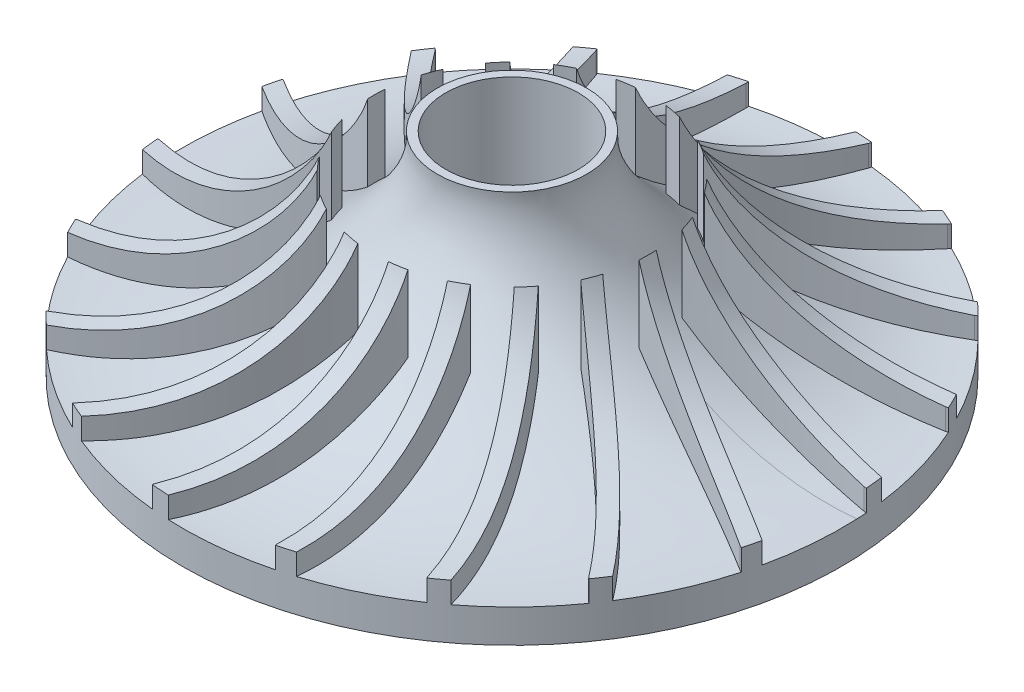
SolidWorks part; units mm, degrees
material "Aluminum Bronze"
ref_plane "Front Plane" through (0, 0, 0) normal (0, 0, 1) x (1, 0, 0)
ref_plane "Top Plane" through (0, 0, 0) normal (0, 1, 0) x (1, 0, 0)
ref_plane "Right Plane" through (0, 0, 0) normal (1, 0, 0) x (0, 0, -1)
curve "Shroud Curve"
curve "Impeller Curve"
curve "Blade Curve"
sketch "Sketch2" plane through (0, 0, 0) normal (0, 0, 1) x (1, 0, 0)
  line L0 (12.3936, 20.32) -> (31.524, 20.32)
  line L1 (31.524, 20.32) -> (31.524, 5.2084)
  spline S0 degree 3 poles (-987.5158, 25.9904) (14.3924, 25.4096) (12.3838, 22.8501) (12.394, 20.2062) (12.3983, 20.0433) (12.4153, 19.7646) (12.4464, 19.455) (12.5, 19.0868) (12.5725, 18.7015) (12.668, 18.288) (12.7893, 17.8459) (12.939, 17.3754) (13.1199, 16.8765) (13.3352, 16.3498) (13.5878, 15.7963) (13.8846, 15.2103) (14.2339, 14.5865) (14.6461, 13.9208) (15.1337, 13.2093) (15.7166, 12.4431) (16.4608, 11.5686) (17.3717, 10.6312) (18.3895, 9.7284) (19.3933, 8.9559) (20.3425, 8.3146) (21.265, 7.7651) (22.1833, 7.2836) (23.1089, 6.8589) (24.0463, 6.4862) (24.992, 6.1646) (25.9534, 5.89) (26.9392, 5.6596) (27.948, 5.4753) (28.9787, 5.3375) (30.0306, 5.2467) (30.8193, 5.2152) (31.2822, 5.2094) (31.3964, 5.2087) (31.4474, 5.2085) (36.9587, 5.195) (42.4601, 7.5368) (46.7066, -994.6744) knots -0.286221 -0.286221 -0.286221 -0.286221 0.000573 0.001147 0.01108 0.018892 0.032537 0.046055 0.060727 0.076613 0.093771 0.112259 0.132129 0.153434 0.17622 0.200532 0.227285 0.256591 0.288558 0.324244 0.364815 0.417623 0.471125 0.517692 0.559977 0.599882 0.638379 0.676541 0.714348 0.751783 0.788827 0.826738 0.865587 0.904104 0.943642 0.984281 0.992833 0.995696 0.997129 0.998564 1.615425 1.615425 1.615425 1.615425 only from (12.3936, 20.32) to (31.524, 5.2084) construction
  spline S1 degree 3 poles (12.3936, 20.32) (12.3936, 20.3149) (12.3937, 20.2945) (12.394, 20.2378) (12.396, 20.1285) (12.4051, 19.9045) (12.4293, 19.6044) (12.4765, 19.2357) (12.5395, 18.8663) (12.6241, 18.4693) (12.7311, 18.0501) (12.8642, 17.6027) (13.0263, 17.1273) (13.2201, 16.6241) (13.4517, 16.0871) (13.7253, 15.5171) (14.049, 14.9088) (14.4286, 14.2638) (14.8748, 13.5782) (15.4055, 12.8419) (16.0542, 12.0336) (16.9755, 11.0153) (18.0099, 10.0444) (19.1028, 9.1708) (20.0247, 8.5203) (20.9547, 7.9421) (21.8752, 7.4382) (22.7956, 6.9963) (23.7195, 6.61) (24.6625, 6.2706) (25.622, 5.9787) (26.6067, 5.7317) (27.6157, 5.5303) (28.6473, 5.3762) (29.7007, 5.2699) (30.5959, 5.2213) (31.1689, 5.2101) (31.3964, 5.2087) (31.4474, 5.2085) (31.4857, 5.2084) (31.5112, 5.2084) (31.524, 5.2084) knots 0 0 0 0 0.000573 0.002299 0.006366 0.012866 0.027514 0.040203 0.054662 0.069638 0.085834 0.103308 0.122113 0.142304 0.163927 0.187868 0.213381 0.24139 0.272007 0.305338 0.34342 0.38851 0.459669 0.502746 0.545774 0.586485 0.625835 0.66373 0.701259 0.738405 0.776386 0.814001 0.852529 0.892045 0.931258 0.971546 0.992833 0.995696 0.997129 0.998564 1 1 1 1
ref_axis "Axis1" through (0, 21.336, 0) along (0, -1, 0)
revolve "Shroud" add sketch "Sketch2" angle 360 about axis through (0, 21.336, 0) along (0, -1, 0)
sketch "Sketch3" plane through (0, 0, 0) normal (0, 0, 1) x (1, 0, 0)
  line L0 (31.5224, 3.1749) -> (31.5224, 0)
  line L1 (31.5224, 0) -> (0, 0)
  line L2 (0, 0) -> (0, 20.32)
  line L3 (31.524, 20.32) -> (-31.524, 20.32) construction
  line L4 (7.1438, 20.3135) -> (0, 20.32)
  spline S7 degree 3 poles (-1987.4593, 163.9747) (15.0815, 23.5909) (7.237, 22.1997) (7.1404, 20.2633) (7.1388, 20.2349) (7.1374, 20.2066) (7.1335, 20.1218) (7.1286, 19.962) (7.1283, 19.6342) (7.1493, 19.2151) (7.2045, 18.7258) (7.2851, 18.2511) (7.3952, 17.7637) (7.5366, 17.2646) (7.7099, 16.7544) (7.9123, 16.2424) (8.1435, 15.7291) (8.4026, 15.2142) (8.6894, 14.6982) (9.0087, 14.1732) (9.361, 13.6396) (9.7473, 13.0984) (10.1682, 12.5501) (10.6246, 11.9955) (11.1243, 11.4283) (11.6762, 10.8425) (12.291, 10.2334) (12.9809, 9.5977) (13.7595, 8.9332) (14.6684, 8.2199) (15.8201, 7.4001) (17.0829, 6.6101) (18.3914, 5.8979) (19.5636, 5.3373) (20.7168, 4.8556) (21.8326, 4.4512) (22.9378, 4.1082) (24.0401, 3.8203) (25.1484, 3.5838) (26.273, 3.396) (27.4131, 3.2573) (28.5804, 3.1676) (29.775, 3.129) (30.6764, 3.1396) (31.2068, 3.16) (31.3443, 3.1662) (31.3995, 3.1688) (31.441, 3.1708) (37.6328, 3.4785) (43.5866, 8.1443) (152.6696, -1993.0178) knots -0.175256 -0.175256 -0.175256 -0.175256 0.000669 0.001536 0.002404 0.00327 0.004136 0.010183 0.017925 0.034167 0.04862 0.063032 0.07828 0.094393 0.110554 0.127643 0.144833 0.162141 0.180455 0.198922 0.218443 0.239045 0.259851 0.281779 0.304858 0.329116 0.35553 0.38416 0.415071 0.449318 0.490018 0.54459 0.585745 0.626499 0.663632 0.700247 0.735233 0.769651 0.80463 0.839062 0.874118 0.909854 0.946332 0.983621 0.992446 0.994976 0.996243 0.99751 0.998779 1.564382 1.564382 1.564382 1.564382 only from (7.1438, 20.3135) to (31.5224, 3.1749) construction
  spline S8 degree 3 poles (7.1438, 20.3135) (7.1431, 20.3062) (7.1417, 20.2895) (7.1404, 20.2633) (7.1388, 20.2349) (7.1374, 20.2066) (7.1335, 20.1218) (7.1286, 19.962) (7.1283, 19.6342) (7.1493, 19.2151) (7.2045, 18.7258) (7.2851, 18.2511) (7.3952, 17.7637) (7.5366, 17.2646) (7.7099, 16.7544) (7.9123, 16.2424) (8.1435, 15.7291) (8.4026, 15.2142) (8.6894, 14.6982) (9.0087, 14.1732) (9.361, 13.6396) (9.7473, 13.0984) (10.1682, 12.5501) (10.6246, 11.9955) (11.1243, 11.4283) (11.6762, 10.8425) (12.291, 10.2334) (12.9809, 9.5977) (13.7595, 8.9332) (14.6684, 8.2199) (15.8201, 7.4001) (17.0829, 6.6101) (18.3914, 5.8979) (19.5636, 5.3373) (20.7168, 4.8556) (21.8326, 4.4512) (22.9378, 4.1082) (24.0401, 3.8203) (25.1484, 3.5838) (26.273, 3.396) (27.4131, 3.2573) (28.5804, 3.1676) (29.775, 3.129) (30.6764, 3.1396) (31.2068, 3.16) (31.3443, 3.1662) (31.3995, 3.1688) (31.441, 3.1708) (31.4819, 3.1728) (31.5091, 3.1742) (31.5224, 3.1749) knots 0 0 0 0 0.000669 0.001536 0.002404 0.00327 0.004136 0.010183 0.017925 0.034167 0.04862 0.063032 0.07828 0.094393 0.110554 0.127643 0.144833 0.162141 0.180455 0.198922 0.218443 0.239045 0.259851 0.281779 0.304858 0.329116 0.35553 0.38416 0.415071 0.449318 0.490018 0.54459 0.585745 0.626499 0.663632 0.700247 0.735233 0.769651 0.80463 0.839062 0.874118 0.909854 0.946332 0.983621 0.992446 0.994976 0.996243 0.99751 0.998779 1 1 1 1
revolve "Impeller" add sketch "Sketch3" angle 360 about axis through (0, 21.336, 0) along (0, -1, 0)
sketch "Sketch6" plane through (0, 0, 0) normal (0, 1, 0) x (1, 0, 0)
  arc A1 (12.2144, -0.7732) -> (12.5729, 0.7732) centre (12.3936, 0) cw
  arc A2 (30.1522, -8.3254) -> (31.0078, -6.9882) centre (30.58, -7.6568) ccw
  arc A4 (30.376, -8.4239) -> (30.7718, -6.8379) centre (0, 0) ccw
  circle A6 centre (0, 0) radius 31.5224 construction
  arc A9 (13.1723, 0.631) -> (13.1496, -0.9982) centre (0, 0) cw
  circle A12 centre (0, 0) radius 12.3936 construction
  circle A13 centre (0, 0) radius 12.3936 construction
  spline S0 degree 3 poles (442.7335, 1953.011) (-2.4115, 1.5934) (5.2104, 1.6686) (12.9096, -0.1198) (14.0469, -0.3996) (15.8438, -0.8995) (18.1748, -1.6376) (20.7354, -2.5797) (23.4794, -3.756) (26.0506, -5.0115) (28.3794, -6.2947) (29.8541, -7.1939) (30.513, -7.6139) (30.5465, -7.6354) (36.7948, -11.6293) (42.0686, -17.1348) (1126.7136, 1665.009) knots -1.118742 -1.118742 -1.118742 -1.118742 0.001002 0.002004 0.077126 0.178187 0.284155 0.446993 0.590825 0.735722 0.879774 0.992981 0.996992 0.997995 0.998997 2.118966 2.118966 2.118966 2.118966 only from (12.3936, 0) to (30.58, -7.6568) construction
  spline S1 degree 3 poles (12.3936, 0) (12.4904, -0.0224) (12.6967, -0.0708) (13.1216, -0.1729) (13.8023, -0.3426) (14.8827, -0.6297) (16.8946, -1.2142) (19.41, -2.0688) (22.2719, -3.2199) (24.8527, -4.4069) (27.3913, -5.7302) (29.2525, -6.8202) (30.2839, -7.4679) (30.5241, -7.6211) (30.5576, -7.6425) (30.5744, -7.6532) (30.58, -7.6568) knots 0 0 0 0 0.015031 0.032062 0.066113 0.121166 0.201187 0.383066 0.522901 0.667756 0.812725 0.955894 0.993984 0.996992 0.998997 1 1 1 1
  spline S2 degree 1 poles (12.2144, -0.7732) (30.1522, -8.3254) knots 0 0 1 1 construction
  spline S3 degree 3 poles (12.2144, -0.7732) (12.4486, -0.8275) (12.8385, -0.9205) (14.4199, -1.315) (17.3224, -2.1524) (21.5335, -3.7174) (25.9586, -5.8069) (28.7797, -7.4473) (30.1522, -8.3254) knots 0 0 0 0 0.036883 0.061471 0.25 0.5 0.75 1 1 1 1
  spline S4 degree 1 poles (12.5729, 0.7732) (31.0078, -6.9882) knots 0 0 1 1 construction
  spline S5 degree 3 poles (12.5729, 0.7732) (12.7229, 0.7385) (12.9728, 0.6796) (14.6003, 0.2844) (17.6768, -0.59) (22.1503, -2.2525) (26.5926, -4.3502) (29.4354, -5.9917) (30.8506, -6.8878) (30.9489, -6.9505) (31.0078, -6.9882) knots 0 0 0 0 0.022988 0.038314 0.25 0.5 0.75 0.982599 0.989559 1 1 1 1
  dimension "D3" = 0.7937
  dimension "D1" = 0.7937
  dimension "D2" = 0.7937
sketch "Sketch5" plane through (0, 0, 0) normal (0, -1, 0) x (1, 0, 0)
  circle A0 centre (0, 0) radius 6.35
  dimension "D1" = 12.7
extrude "Shaft Hole" cut sketch "Sketch5" against normal through all
extrude "Boss-Extrude2" add sketch "Sketch6" along normal through all contours S5 A1 A9 S1 A4 | A9 S3 A2 A4 S1 region at (22.0258, 0, 3.8518) region at (22.1341, 0, 3.036)
pattern_circular "CirPattern1" count 18 over 360 about axis through (0, 21.336, 0) along (0, -1, 0) of "Boss-Extrude2"
revolve "Cut-Revolve1" cut sketch "Sketch2<3>" angle 360 about axis through (0, 21.336, 0) along (0, -1, 0)
sketch "Sketch2<3>" plane through (0, 0, 0) normal (0, 0, 1) x (1, 0, 0) same geometry as "Sketch2"
